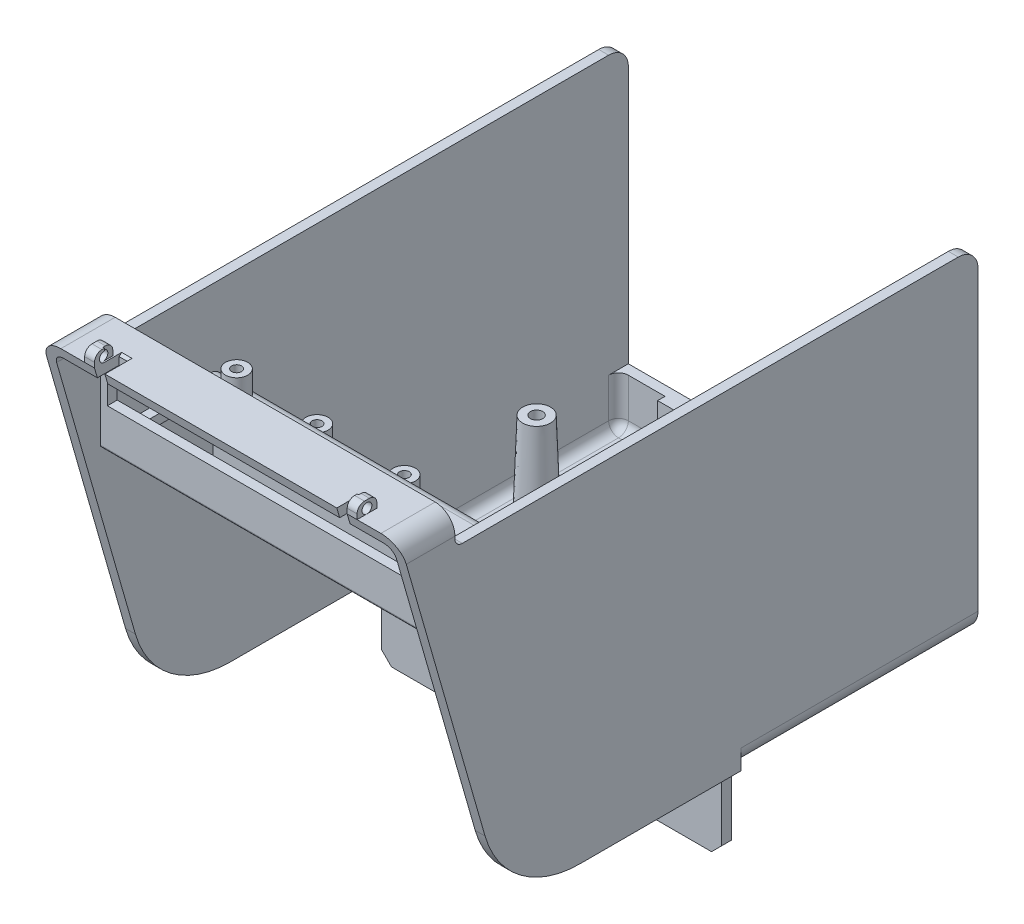
SolidWorks part; units mm, degrees
ref_plane "Front Plane" through (0, 0, 0) normal (0, 0, 1) x (1, 0, 0)
ref_plane "Top Plane" through (0, 0, 0) normal (0, 1, 0) x (1, 0, 0)
ref_plane "Right Plane" through (0, 0, 0) normal (1, 0, 0) x (0, 0, -1)
sketch "Sketch1" plane through (0, 0, 0) normal (0, 1, 0) x (1, 0, 0)
  line L1 (-36.425, -54.49) -> (36.425, -54.49)
  line L2 (-36.425, -54.49) -> (-36.425, 54.49)
  line L3 (-36.425, 54.49) -> (36.425, 54.49)
  line L4 (36.425, -54.49) -> (36.425, 54.49)
  line L5 (-36.425, -54.49) -> (36.425, 54.49) construction
  line L6 (-36.425, 54.49) -> (36.425, -54.49) construction
  point P0 (0, 0)
  dimension "D1" = 72.85
  dimension "D2" = 108.98
extrude "Boss-Extrude1" add sketch "Sketch1" along normal blind 66.66 and the other way blind 7.5
sketch "Sketch2" plane through (36.425, 0, 0) normal (1, 0, 0) x (0, 0, -1)
  line L0 (-54.49, 66.66) -> (-54.49, 43.24)
  line L1 (-54.49, 66.66) -> (-54.49, -7.5) construction
  line L2 (-54.49, 43.24) -> (-31.71, 43.24)
  line L3 (-31.71, 43.24) -> (-31.71, 25.46)
  line L4 (-31.71, 25.46) -> (-14.01, 25.46)
  line L5 (-14.01, 25.46) -> (-14.01, 7.68)
  line L6 (-14.01, 7.68) -> (2.51, 7.68)
  line L7 (2.51, 7.68) -> (2.51, -7.5)
  line L8 (-54.49, -7.5) -> (54.49, -7.5) construction
  line L9 (54.49, 66.66) -> (54.49, -7.5) construction
  line L10 (-54.49, 66.66) -> (54.49, 66.66) construction
  dimension "D1" = 23.42
  dimension "D2" = 86.2
  dimension "D3" = 41.2
  dimension "D4" = 58.98
  dimension "D5" = 68.5
  dimension "D6" = 51.98
extrude "Cut-Extrude1" cut sketch "Sketch2" against normal through all and the other way through all flip side to cut
fillet "Fillet1" radius 0.5 6 edges at (0, 7.68, -2.51) (0, 25.46, 14.01) (0, 43.24, 31.71) (0, 43.24, 54.49) (0, 25.46, 31.71) (0, 7.68, 14.01)
shell "Shell1" thickness 2
sketch "Sketch3" plane through (0, 43.24, 0) normal (0, -1, 0) x (1, 0, 0)
  line L0 (-36.425, 54.49) -> (36.425, 54.49) construction
  line L1 (-32.5, 47.39) -> (32.5, 47.39)
  line L2 (-32.5, 47.39) -> (-32.5, 37.39)
  line L3 (-32.5, 37.39) -> (32.5, 37.39)
  line L4 (32.5, 47.39) -> (32.5, 37.39)
  line L5 (0, 0) -> (0, 59.3951) construction
  dimension "D1" = 65
  dimension "D2" = 10
  dimension "D3" = 7.1
extrude "Cut-Extrude2" cut sketch "Sketch3" against normal up to next
sketch "Sketch4" plane through (0, 25.46, 0) normal (0, -1, 0) x (1, 0, 0)
  line L0 (-32.5, 47.39) -> (-32.5, 37.39) construction
  line L1 (-32.5, 29.61) -> (32.5, 29.61)
  line L2 (-32.5, 29.61) -> (-32.5, 19.61)
  line L3 (-32.5, 19.61) -> (32.5, 19.61)
  line L4 (32.5, 29.61) -> (32.5, 19.61)
  line L5 (32.5, 37.39) -> (32.5, 47.39) construction
  line L6 (36.425, 31.71) -> (-36.425, 31.71) construction
  dimension "D1" = 2.1
  dimension "D2" = 10
extrude "Cut-Extrude3" cut sketch "Sketch4" against normal up to next
sketch "Sketch5" plane through (0, 7.68, 0) normal (0, -1, 0) x (1, 0, 0)
  line L0 (-32.5, 29.61) -> (-32.5, 19.61) construction
  line L1 (-32.5, 11.91) -> (32.5, 11.91)
  line L2 (-32.5, 11.91) -> (-32.5, 1.91)
  line L3 (-32.5, 1.91) -> (32.5, 1.91)
  line L4 (32.5, 11.91) -> (32.5, 1.91)
  line L5 (32.5, 19.61) -> (32.5, 29.61) construction
  line L6 (36.425, 14.01) -> (-36.425, 14.01) construction
  dimension "D1" = 10
  dimension "D2" = 2.1
extrude "Cut-Extrude4" cut sketch "Sketch5" against normal up to next
sketch "Sketch7" plane through (0, 45.24, 0) normal (0, 1, 0) x (1, 0, 0)
  line L1 (-36.425, -54.49) -> (36.425, -54.49) construction
  circle A0 centre (-28, -33.29) radius 2.25
  circle A1 centre (28, -33.29) radius 2.25
  dimension "D1" = 4.5
  dimension "D4" = 28
  dimension "D5" = 4.5
  dimension "D2" = 28
  dimension "D3" = 21.2
extrude "Boss-Extrude2" add sketch "Sketch7" along normal blind 4.5 and the other way up to next
sketch "Sketch8" plane through (0, 27.46, 0) normal (0, 1, 0) x (1, 0, 0)
  line L0 (-32.5, -19.61) -> (32.5, -19.61) construction
  circle A0 centre (-28, -17.01) radius 2.25
  circle A1 centre (28, -17.01) radius 2.25
  dimension "D1" = 28
  dimension "D4" = 4.5
  dimension "D2" = 28
  dimension "D3" = 2.6
extrude "Boss-Extrude3" add sketch "Sketch8" along normal blind 4.5 and the other way up to next (2 mm away)
sketch "Sketch9" plane through (0, 9.68, 0) normal (0, 1, 0) x (1, 0, 0)
  line L0 (-32.5, -1.91) -> (32.5, -1.91) construction
  circle A0 centre (-28, 0.69) radius 2.25
  circle A1 centre (28, 0.69) radius 2.25
  dimension "D1" = 4.5
  dimension "D3" = 28
  dimension "D5" = 4.5
  dimension "D2" = 2.6
  dimension "D4" = 28
extrude "Boss-Extrude4" add sketch "Sketch9" along normal blind 4.5 and the other way up to next
sketch "Sketch10" plane through (0, 0, 54.49) normal (0, 0, 1) x (1, 0, 0)
  line L0 (-32.5, 51.34) -> (-22.5, 51.34) construction
  line L1 (-33, 57.84) -> (33, 57.84)
  line L2 (-33, 57.84) -> (-33, 51.34)
  line L3 (-33, 51.34) -> (33, 51.34)
  line L4 (33, 57.84) -> (33, 51.34)
  line L5 (-33, 51.34) -> (-33, 49.74) construction
  line L6 (33, 51.34) -> (33, 49.74) construction
  line L7 (-32.5, 53.84) -> (-22.5, 53.84) construction
  dimension "D1" = 4
extrude "Cut-Extrude5" cut sketch "Sketch10" against normal up to next
sketch "Sketch11" plane through (0, -5.5, 0) normal (0, 1, 0) x (1, 0, 0)
  line L0 (34.425, 54.49) -> (-34.425, 54.49) construction
  line L1 (0, 0) -> (0, 57.5418) construction
  circle A0 centre (-25, 24.49) radius 3.5
  circle A1 centre (25, 24.49) radius 3.5
  dimension "D1" = 7
  dimension "D2" = 7
  dimension "D3" = 30
  dimension "D4" = 50
extrude "Boss-Extrude5" add sketch "Sketch11" along normal blind 19.72 draft 2
sketch "Sketch12" plane through (-36.425, 0, 0) normal (-1, 0, 0) x (0, 0, 1)
  line L0 (54.49, 66.66) -> (64.49, 66.66)
  line L1 (-54.49, -7.5) -> (-2.51, -7.5) construction
  line L2 (64.49, 66.66) -> (47.3791, 6.9873)
  line L4 (-54.49, -7.5) -> (28.1539, -7.5)
  line L5 (-54.49, -7.5) -> (54.49, 66.66)
  arc A1 (47.3791, 6.9873) -> (28.1539, -7.5) centre (28.1539, 12.5) cw
  dimension "D2" = 20
  dimension "D1" = 10
  dimension "D5" = 74
extrude "Boss-Extrude6" add sketch "Sketch12" against normal blind 2
mirror "Mirror1" about plane through (0, 0, 0) normal (1, 0, 0) of "Boss-Extrude6"
sketch "Sketch20" plane through (0, 66.66, 0) normal (0, 1, 0) x (1, 0, 0)
  line L1 (-34.425, -64.49) -> (34.425, -64.49)
  line L2 (-34.425, -64.49) -> (-34.425, -54.49)
  line L3 (-34.425, -54.49) -> (34.425, -54.49)
  line L4 (34.425, -64.49) -> (34.425, -54.49)
extrude "Boss-Extrude7" add sketch "Sketch20" against normal blind 2
sketch "Sketch21" plane through (36.425, 0, 0) normal (1, 0, 0) x (0, 0, -1)
  line L0 (-64.49, 66.66) -> (-63.7125, 63.9486)
  line L1 (-47.3791, 6.9873) -> (-64.49, 66.66) construction
  line L2 (-63.7125, 63.9486) -> (-66.4372, 63.9486)
  line L3 (-66.4372, 63.9486) -> (-64.49, 66.66)
extrude "Cut-Extrude12" cut sketch "Sketch21" against normal through all
chamfer "Chamfer1" [suppressed] distance 4 angle 15
fillet "Fillet3" [suppressed] radius 1
sketch "Sketch13" plane through (0, -7.5, 0) normal (0, -1, 0) x (1, 0, 0)
  line L1 (-34.425, -54.49) -> (34.425, -54.49)
  line L2 (-34.425, -54.49) -> (-34.425, -51.99)
  line L3 (-34.425, -51.99) -> (34.425, -51.99)
  line L4 (34.425, -54.49) -> (34.425, -51.99)
  dimension "D1" = 2.5
extrude "Cut-Extrude6" cut sketch "Sketch13" against normal up to next
fillet "Fillet4" radius 3 2 edges at (-35.425, 66.66, -54.49) (35.425, 66.66, -54.49)
sketch "Sketch14" plane through (0, 66.66, 0) normal (0, 1, 0) x (1, 0, 0)
  line L11 (-35.425, 64.9406) -> (35.425, 64.9406)
  line L15 (-35.425, -32.21) -> (-35.425, -53.49)
  line L17 (-35.425, -53.49) -> (35.425, -53.49)
  line L18 (35.425, -53.49) -> (35.425, 51.49)
  line L19 (-35.425, 64.9406) -> (-35.425, -53.49)
  line L20 (-35.425, -53.49) -> (35.425, -53.49)
  line L21 (35.425, -53.49) -> (35.425, 64.9406)
  dimension "D1" = 1
extrude "Cut-Extrude7" cut sketch "Sketch14" against normal blind 1.5
sketch "Sketch16" plane through (0, -7.5, 0) normal (0, -1, 0) x (1, 0, 0)
  line L0 (34.425, -51.99) -> (-34.425, -51.99) construction
  circle A0 centre (-25, -24.49) radius 1.25
  circle A1 centre (25, -24.49) radius 1.25
  dimension "D1" = 2.5
  dimension "D2" = 2.5
  dimension "D3" = 27.5
  dimension "D4" = 27.5
extrude "Cut-Extrude8" cut sketch "Sketch16" against normal up to next
sketch "Sketch17" plane through (0, 14.18, 0) normal (0, 1, 0) x (1, 0, 0)
  circle A0 centre (-28, 0.69) radius 1
  circle A1 centre (28, 0.69) radius 1
  dimension "D1" = 2
  dimension "D2" = 2
extrude "Cut-Extrude9" cut sketch "Sketch17" against normal blind 4
sketch "Sketch18" plane through (0, 31.96, 0) normal (0, 1, 0) x (1, 0, 0)
  circle A0 centre (-28, -17.01) radius 1
  circle A1 centre (28, -17.01) radius 1
  dimension "D1" = 2
  dimension "D2" = 2
extrude "Cut-Extrude10" cut sketch "Sketch18" against normal blind 4
sketch "Sketch19" plane through (0, 49.74, 0) normal (0, 1, 0) x (1, 0, 0)
  circle A0 centre (-28, -33.29) radius 1
  circle A1 centre (28, -33.29) radius 1
  dimension "D1" = 2
  dimension "D2" = 2
extrude "Cut-Extrude11" cut sketch "Sketch19" against normal blind 4
sketch "Sketch22" plane through (36.425, 0, 0) normal (1, 0, 0) x (0, 0, -1)
  line L0 (54.49, 63.66) -> (54.49, -7.5) construction
  line L1 (54.49, 60.66) -> (-53.49, 60.66)
  line L2 (54.49, 60.66) -> (54.49, 66.66)
  line L3 (54.49, 66.66) -> (-53.49, 66.66)
  line L4 (-53.49, 60.66) -> (-53.49, 66.66)
  line L5 (48.51, 60.66) -> (-51.99, 60.66) construction
extrude "Cut-Extrude13" cut sketch "Sketch22" against normal through all
sketch "Sketch23" plane through (0, 60.66, 0) normal (0, 1, 0) x (1, 0, 0)
  line L1 (-34.425, -52.49) -> (34.425, -52.49)
  line L2 (-34.425, -52.49) -> (-34.425, -53.49)
  line L3 (-34.425, -53.49) -> (34.425, -53.49)
  line L4 (34.425, -52.49) -> (34.425, -53.49)
  line L5 (34.425, -52.49) -> (34.425, -32.21) construction
  line L6 (-36.425, -53.49) -> (36.425, -53.49) construction
extrude "Boss-Extrude8" add sketch "Sketch23" along normal offset from surface (4 mm away) 2
fillet "Fillet6" radius 2 2 edges at (-34.425, 64.66, 52.99) (34.425, 64.66, 52.99)
fillet "Fillet7" radius 2 2 edges at (34.425, 64.66, 59.2033) (-34.425, 64.66, 59.2033)
fillet "Fillet8" radius 4 2 edges at (36.425, 66.66, 58.99) (-36.425, 66.66, 58.99)
sketch "Sketch28" plane through (0, -7.5, 0) normal (0, -1, 0) x (1, 0, 0)
  line L0 (34.425, -2.51) -> (34.425, 28.1539) construction
  line L1 (-34.425, -2.51) -> (34.425, -2.51)
  line L2 (-34.425, -2.51) -> (-34.425, -4.51)
  line L3 (-34.425, -4.51) -> (34.425, -4.51)
  line L4 (34.425, -2.51) -> (34.425, -4.51)
  dimension "D1" = 2
extrude "Boss-Extrude10" add sketch "Sketch28" along normal blind 15.2
chamfer "Chamfer2" distance 2 angle 45 2 edges at (-34.425, -22.7, -3.51) (34.425, -22.7, -3.51)
sketch "Sketch29" plane through (0, 0, -2.51) normal (0, 0, 1) x (1, 0, 0)
  line L0 (-24.425, -14.7) -> (24.425, -14.7) construction
  line L1 (0, 0) -> (0, -14.7) construction
  line L2 (32.425, -22.7) -> (-32.425, -22.7) construction
  circle A0 centre (-24.425, -14.7) radius 1.75
  circle A1 centre (24.425, -14.7) radius 1.75
  dimension "D3" = 3.5
  dimension "D1" = 8
  dimension "D2" = 48.85
extrude "Cut-Extrude16" cut sketch "Sketch29" against normal through all
fillet "Fillet10" radius 2 2 edges at (34.425, -5.5, -28.25) (-34.425, -5.5, -28.25)
sketch "Sketch30" plane through (0, 0, -54.49) normal (0, 0, -1) x (-1, 0, 0)
  line L0 (-36.425, -3.5) -> (-36.425, -7.5)
  line L1 (-36.425, -7.5) -> (-32.425, -7.5)
  line L2 (0, -7.5) -> (0, 0) construction
  line L3 (34.425, -7.5) -> (-34.425, -7.5) construction
  line L4 (36.425, -7.5) -> (32.425, -7.5)
  line L5 (36.425, -3.5) -> (36.425, -7.5)
  arc A1 (-36.425, -3.5) -> (-32.425, -7.5) centre (-32.425, -3.5) ccw
  arc A2 (-34.425, -3.5) -> (-32.425, -5.5) centre (-32.425, -3.5) ccw construction
  arc A3 (36.425, -3.5) -> (32.425, -7.5) centre (32.425, -3.5) cw
  dimension "D1" = 8
extrude "Cut-Extrude17" cut sketch "Sketch30" against normal up to surface (49.98 mm away) up to face at (26.175, -14.7, -4.51)
sketch "Sketch31" plane through (0, 0, 0) normal (-1, 0, 0) x (0, 0, 1)
  line L0 (-4.51, -7.5) -> (-51.99, -7.5) construction
  line L1 (-54.49, 60.66) -> (-51.99, 60.66)
  line L2 (-54.49, 60.66) -> (-54.49, -7.5)
  line L3 (-54.49, -7.5) -> (-51.99, -7.5)
  line L4 (-51.99, 60.66) -> (-51.99, -7.5)
  line L5 (-51.99, -3.5) -> (-51.99, -6.9641) construction
extrude "Cut-Extrude18" cut sketch "Sketch31" against normal mid plane 179.66
sketch "Sketch32" plane through (0, 0, -51.99) normal (0, 0, -1) x (-1, 0, 0)
  line L8 (-34.425, -3.5) -> (-34.425, 60.66)
  line L9 (-34.425, 60.66) -> (-36.425, 60.66)
  line L10 (-36.425, 60.66) -> (-36.425, -3.5)
  line L11 (-32.425, -7.5) -> (32.425, -7.5)
  line L12 (36.425, -3.5) -> (36.425, 60.66)
  line L13 (36.425, 60.66) -> (34.425, 60.66)
  line L14 (34.425, 60.66) -> (34.425, -3.5)
  line L15 (32.425, -5.5) -> (-32.425, -5.5)
  line L16 (-34.425, -3.5) -> (-34.425, 60.66)
  line L17 (-34.425, 60.66) -> (-36.425, 60.66)
  line L18 (-36.425, 60.66) -> (-36.425, -3.5)
  line L19 (-32.425, -7.5) -> (32.425, -7.5)
  line L20 (36.425, -3.5) -> (36.425, 60.66)
  line L21 (36.425, 60.66) -> (34.425, 60.66)
  line L22 (34.425, 60.66) -> (34.425, -3.5)
  line L23 (32.425, -5.5) -> (-32.425, -5.5)
  arc A3 (-34.425, -3.5) -> (-32.425, -5.5) centre (-32.425, -3.5) ccw
  arc A4 (-36.425, -3.5) -> (-32.425, -7.5) centre (-32.425, -3.5) ccw
  arc A5 (32.425, -5.5) -> (34.425, -3.5) centre (32.425, -3.5) ccw
  arc A6 (-34.425, -3.5) -> (-32.425, -5.5) centre (-32.425, -3.5) ccw
  arc A7 (-36.425, -3.5) -> (-32.425, -7.5) centre (-32.425, -3.5) ccw
  arc A8 (32.425, -5.5) -> (34.425, -3.5) centre (32.425, -3.5) ccw
  arc A10 (32.425, -7.5) -> (36.425, -3.5) centre (32.425, -3.5) ccw
  arc A11 (32.425, -7.5) -> (36.425, -3.5) centre (32.425, -3.5) ccw
  dimension "D1" = 0
extrude "Boss-Extrude11" add sketch "Sketch32" along normal blind 0.52
sketch "Sketch33" plane through (0, -5.5, 0) normal (0, 1, 0) x (1, 0, 0)
  line L0 (34.425, 52.51) -> (34.425, 4.51) construction
  line L1 (-34.425, 52.51) -> (34.425, 52.51)
  line L2 (-34.425, 52.51) -> (-34.425, 50.51)
  line L3 (-34.425, 50.51) -> (34.425, 50.51)
  line L4 (34.425, 52.51) -> (34.425, 50.51)
  dimension "D1" = 2
extrude "Boss-Extrude12" add sketch "Sketch33" along normal blind 10
fillet "Fillet11" radius 2 5 edges at (33.8392, -4.9142, -50.51) (-34.425, 0.5, -50.51) (-33.8392, -4.9142, -50.51) (0, -5.5, -50.51) (34.425, 0.5, -50.51)
fillet "Fillet12" radius 4 2 edges at (35.425, 60.66, -52.51) (-35.425, 60.66, -52.51)
fillet "Fillet13" radius 1.5 2 edges at (35.425, 60.66, 53.49) (-35.425, 60.66, 53.49)
sketch "Sketch34" plane through (0, -5.5, 0) normal (0, 1, 0) x (1, 0, 0)
  line L0 (-32.425, 50.51) -> (32.425, 50.51) construction
  line L1 (-25, 50.51) -> (-19, 50.51)
  line L2 (-25, 50.51) -> (-25, 49.01)
  line L3 (-25, 49.01) -> (-19, 49.01)
  line L4 (-19, 50.51) -> (-19, 49.01)
  line L5 (0, 0) -> (0, 52.51) construction
  line L6 (34.425, 52.51) -> (-34.425, 52.51) construction
  line L7 (-22, 49.01) -> (-22, 50.51) construction
  line L8 (-32.425, 50.51) -> (32.425, 50.51) construction
  dimension "D1" = 1.5
  dimension "D2" = 6
  dimension "D3" = 22
extrude "Boss-Extrude13" add sketch "Sketch34" along normal up to surface (10 mm away) up to face at (0, 4.5, -50.6481)
sketch "Sketch35" plane through (0, 0, -52.51) normal (0, 0, -1) x (-1, 0, 0)
  line L0 (22, 0.5) -> (22, 4.5) construction
  line L2 (-34.425, 4.5) -> (34.425, 4.5) construction
  line L3 (25, 4.5) -> (19, 4.5) construction
  circle A0 centre (22, 0.5) radius 1.1
  dimension "D1" = 2.2
  dimension "D2" = 4
extrude "Cut-Extrude19" cut sketch "Sketch35" against normal up to surface (3.5 mm away) up to face at (-22, -0.4682, -49.01)
mirror "Mirror2" about plane through (0, 0, 0) normal (1, 0, 0) of "Cut-Extrude19", "Boss-Extrude13"
fillet "Fillet14" radius 2 1 edges at (0, 64.66, 54.49)
sketch "Sketch37" plane through (0, 0, 52.49) normal (0, 0, 1) x (1, 0, 0)
  line L0 (-32.425, 64.66) -> (32.425, 64.66) construction
  line L1 (-23, 64.66) -> (-15, 64.66) construction
  line L2 (-23, 64.66) -> (-23, 63.16) construction
  line L3 (-23, 63.16) -> (-15, 63.16) construction
  line L4 (-15, 64.66) -> (-15, 63.16) construction
  line L5 (34.425, 62.66) -> (-34.425, 62.66) construction
  line L6 (-23.5, 64.66) -> (-14.5, 64.66)
  line L7 (-23.5, 64.66) -> (-23.5, 62.66)
  line L8 (-23.5, 62.66) -> (-14.5, 62.66)
  line L9 (-14.5, 64.66) -> (-14.5, 62.66)
  line L10 (0, 0) -> (0, 66.66) construction
  line L11 (32.425, 66.66) -> (-32.425, 66.66) construction
  line L12 (15, 64.66) -> (15, 63.16) construction
  line L13 (23, 63.16) -> (15, 63.16) construction
  line L14 (23, 64.66) -> (23, 63.16) construction
  line L15 (23, 64.66) -> (15, 64.66) construction
  line L16 (14.5, 64.66) -> (14.5, 62.66)
  line L17 (23.5, 62.66) -> (14.5, 62.66)
  line L18 (23.5, 64.66) -> (23.5, 62.66)
  line L19 (23.5, 64.66) -> (14.5, 64.66)
  line L20 (-23, 64.16) -> (-23, 64.66) construction
  dimension "D1" = 0.5
  dimension "D2" = 0.5
extrude "Cut-Extrude20" cut sketch "Sketch37" along normal through all
sketch "Sketch39" plane through (0, 64.66, 0) normal (0, -1, 0) x (1, 0, 0)
  line L1 (-23.5, 62.9165) -> (-25, 62.9165)
  line L2 (-23.5, 62.9165) -> (-23.5, 54.49)
  line L3 (-23.5, 54.49) -> (-25, 54.49)
  line L4 (-25, 62.9165) -> (-25, 54.49)
  line L5 (-23.5, 54.49) -> (-34.425, 54.49) construction
  line L6 (-23.5, 53.49) -> (-23.5, 52.49) construction
  line L7 (-32.425, 63.9165) -> (32.425, 63.9165) construction
  dimension "D1" = 1.5
  dimension "D2" = 1
sketch "Sketch41" plane through (0, 66.66, 0) normal (0, 1, 0) x (1, 0, 0)
  line L0 (32.425, -64.49) -> (-32.425, -64.49) construction
  line L1 (-25.6, -64.49) -> (-27.6, -64.49)
  line L2 (-25.6, -64.49) -> (-25.6, -60.49)
  line L3 (-25.6, -60.49) -> (-27.6, -60.49)
  line L4 (-27.6, -64.49) -> (-27.6, -60.49)
  dimension "D1" = 4
  dimension "D2" = 2
  dimension "D3" = 25.6
extrude "Boss-Extrude15" add sketch "Sketch41" along normal blind 2.5
sketch "Sketch43" plane through (-25.6, 0, 0) normal (1, 0, 0) x (0, 0, -1)
  line L3 (-62.49, 67.66) -> (-62.49, 69.16) construction
  line L4 (-60.49, 69.16) -> (-64.49, 69.16) construction
  line L5 (-64.49, 66.66) -> (-60.49, 66.66) construction
  circle A0 centre (-62.49, 67.66) radius 1
  dimension "D1" = 2
extrude "Cut-Extrude22" cut sketch "Sketch43" against normal up to surface (2 mm away) up to face at (-27.6, 67.91, 62.49)
fillet "Fillet16" radius 1.5 2 edges at (-26.6, 69.16, 60.49) (-26.6, 69.16, 64.49)
mirror "Mirror3" about plane through (0, 0, 0) normal (1, 0, 0) of "Fillet16", "Cut-Extrude22", "Boss-Extrude15"
sketch "Sketch44" plane through (0, 66.66, 0) normal (0, 1, 0) x (1, 0, 0)
  line L0 (-23.5, -60.49) -> (-23.5, -64.49)
  line L1 (-25.6, -64.49) -> (-23.5, -64.49)
  line L2 (-25.6, -64.49) -> (-25.6, -60.49)
  line L3 (-25.6, -60.49) -> (-23.5, -60.49)
  line L4 (25.6, -64.49) -> (25.6, -60.49)
  line L5 (23.5, -60.49) -> (23.5, -64.49)
  line L6 (23.5, -60.49) -> (25.6, -60.49)
  line L7 (23.5, -64.49) -> (25.6, -64.49)
  dimension "D1" = 2.1
  dimension "D2" = 2.1
extrude "Cut-Extrude23" cut sketch "Sketch44" against normal up to surface (2 mm away) up to face at (0, 64.66, 56.7278)
sketch "Sketch45" plane through (0, 0, 37.39) normal (0, 0, 1) x (1, 0, 0)
  line L4 (-32.5, 45.24) -> (-32.5, 43.24)
  line L5 (-32.5, 43.24) -> (32.5, 43.24)
  line L6 (32.5, 43.24) -> (32.5, 45.24)
  line L7 (32.5, 45.24) -> (-32.5, 45.24)
  line L8 (-32.5, 45.24) -> (-32.5, 43.24)
  line L9 (-32.5, 43.24) -> (32.5, 43.24)
  line L10 (32.5, 43.24) -> (32.5, 45.24)
  line L11 (32.5, 45.24) -> (-32.5, 45.24)
  dimension "D1" = 0
extrude "Cut-Extrude24" cut sketch "Sketch45" against normal blind 1.5
sketch "Sketch46" plane through (0, 0, 29.61) normal (0, 0, -1) x (-1, 0, 0)
  line L4 (-32.5, 27.46) -> (-32.5, 25.46)
  line L5 (-32.5, 25.46) -> (32.5, 25.46)
  line L6 (32.5, 25.46) -> (32.5, 27.46)
  line L7 (32.5, 27.46) -> (-32.5, 27.46)
  line L8 (-32.5, 27.46) -> (-32.5, 25.46)
  line L9 (-32.5, 25.46) -> (32.5, 25.46)
  line L10 (32.5, 25.46) -> (32.5, 27.46)
  line L11 (32.5, 27.46) -> (-32.5, 27.46)
  dimension "D1" = 0
extrude "Cut-Extrude25" cut sketch "Sketch46" against normal up to surface (0.1 mm away) up to face at (0, 35.1, 29.71)
sketch "Sketch47" plane through (0, 0, 11.91) normal (0, 0, -1) x (-1, 0, 0)
  line L4 (-32.5, 9.68) -> (-32.5, 7.68)
  line L5 (-32.5, 7.68) -> (32.5, 7.68)
  line L6 (32.5, 7.68) -> (32.5, 9.68)
  line L7 (32.5, 9.68) -> (-32.5, 9.68)
  line L8 (-32.5, 9.68) -> (-32.5, 7.68)
  line L9 (-32.5, 7.68) -> (32.5, 7.68)
  line L10 (32.5, 7.68) -> (32.5, 9.68)
  line L11 (32.5, 9.68) -> (-32.5, 9.68)
  dimension "D1" = 0
extrude "Cut-Extrude26" cut sketch "Sketch47" against normal up to surface (0.1 mm away) up to face at (0, 17.32, 12.01)
sketch "Sketch48" plane through (0, 0, 47.39) normal (0, 0, -1) x (-1, 0, 0)
  line L4 (-32.5, 45.24) -> (-32.5, 43.24)
  line L5 (-32.5, 43.24) -> (32.5, 43.24)
  line L6 (32.5, 43.24) -> (32.5, 45.24)
  line L7 (32.5, 45.24) -> (-32.5, 45.24)
  line L8 (-32.5, 45.24) -> (-32.5, 43.24)
  line L9 (-32.5, 43.24) -> (32.5, 43.24)
  line L10 (32.5, 43.24) -> (32.5, 45.24)
  line L11 (32.5, 45.24) -> (-32.5, 45.24)
  dimension "D1" = 0
extrude "Boss-Extrude16" add sketch "Sketch48" along normal blind 1
sketch "Sketch50" plane through (-25.6, 0, 0) normal (1, 0, 0) x (0, 0, -1)
  line L0 (-60.49, 67.66) -> (-60.49, 66.66) construction
  line L1 (-62.49, 69.16) -> (-60.49, 69.16)
  line L2 (-62.49, 69.16) -> (-62.49, 66.66)
  line L3 (-62.49, 66.66) -> (-60.49, 66.66)
  line L4 (-60.49, 69.16) -> (-60.49, 66.66)
  line L5 (-62.99, 69.16) -> (-61.99, 69.16) construction
  line L6 (-62.49, 66.66) -> (-62.49, 67.66) construction
  circle A0 centre (-62.49, 67.66) radius 1 construction
extrude "Cut-Extrude27" cut sketch "Sketch50" against normal blind 0.3
sketch "Sketch51" plane through (25.6, 0, 0) normal (-1, 0, 0) x (0, 0, 1)
  line L0 (62.49, 69.16) -> (60.49, 69.16) construction
  line L1 (60.49, 69.16) -> (60.49, 66.66) construction
  line L2 (62.49, 66.66) -> (60.49, 66.66) construction
  line L3 (62.49, 69.16) -> (62.49, 66.66) construction
  line L4 (62.49, 69.16) -> (60.49, 69.16)
  line L5 (60.49, 69.16) -> (60.49, 66.66)
  line L6 (62.49, 66.66) -> (60.49, 66.66)
  line L7 (62.49, 69.16) -> (62.49, 66.66)
extrude "Cut-Extrude28" cut sketch "Sketch51" against normal blind 0.3
sketch "Sketch52" plane through (0, 0, 60.49) normal (0, 0, 1) x (1, 0, 0)
  line L2 (-23.5, 64.66) -> (-25.6, 64.66)
  line L3 (-23.5, 64.66) -> (-23.5, 66.66)
  line L4 (-23.5, 66.66) -> (-25.6, 66.66)
  line L6 (0, 0) -> (0, 51.34) construction
  line L7 (-33, 51.34) -> (33, 51.34) construction
  line L8 (23.5, 64.66) -> (25.6, 64.66)
  line L9 (23.5, 64.66) -> (23.5, 66.66)
  line L10 (23.5, 66.66) -> (25.6, 66.66)
  line L11 (25.6, 64.66) -> (25.6, 66.66)
  line L12 (-25.6, 64.66) -> (-25.6, 66.66)
extrude "Cut-Extrude29" cut sketch "Sketch52" against normal blind 1
chamfer "Chamfer3" distance 0.5 angle 45 2 edges at (24.55, 66.66, 59.49) (-24.55, 66.66, 59.49)
